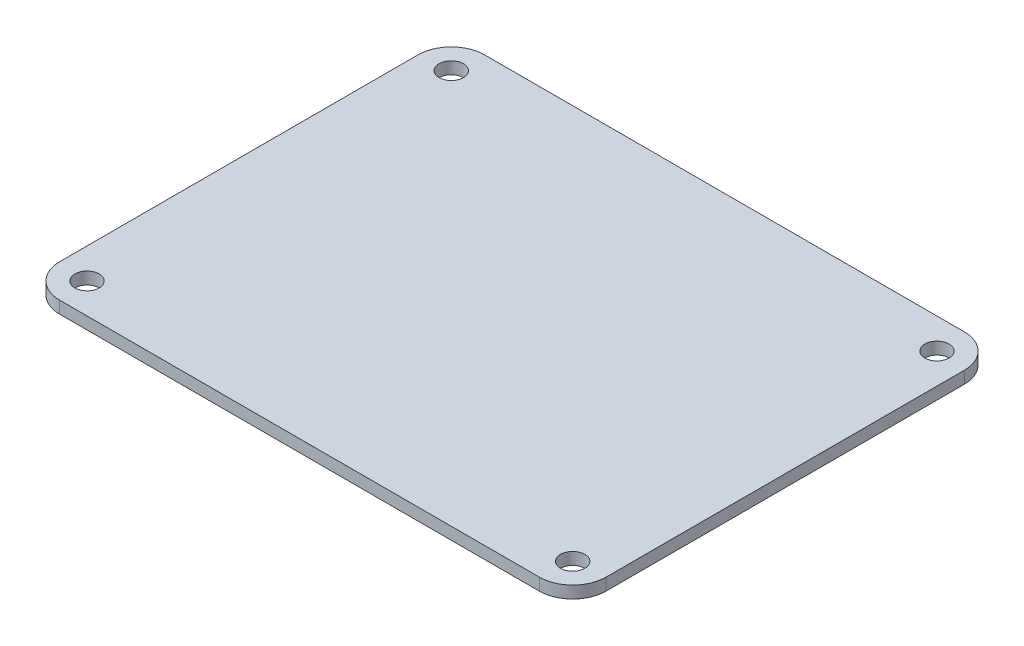
SolidWorks part; units mm, degrees
ref_plane "Front Plane" through (0, 0, 0) normal (0, 0, 1) x (1, 0, 0)
ref_plane "Top Plane" through (0, 0, 0) normal (0, 1, 0) x (1, 0, 0)
ref_plane "Right Plane" through (0, 0, 0) normal (1, 0, 0) x (0, 0, -1)
sketch "Sketch1" plane through (0, 0, 0) normal (0, 1, 0) x (1, 0, 0)
  line L1 (-114.3, 88.9) -> (114.3, 88.9)
  line L2 (-114.3, 88.9) -> (-114.3, -88.9)
  line L3 (-114.3, -88.9) -> (114.3, -88.9)
  line L4 (114.3, 88.9) -> (114.3, -88.9)
  line L5 (-114.3, 88.9) -> (114.3, -88.9) construction
  line L6 (-114.3, -88.9) -> (114.3, 88.9) construction
  point P0 (0, 0)
  dimension "D1" = 177.8
  dimension "10" = 228.6
extrude "Boss-Extrude1" add sketch "Sketch1" along normal blind 5.08
sketch "Sketch2" plane through (0, 5.08, 0) normal (0, 1, 0) x (1, 0, 0)
  line L0 (-101.6, 76.2) -> (-101.6, 88.9) construction
  line L1 (114.3, 88.9) -> (-114.3, 88.9) construction
  line L2 (-101.6, 76.2) -> (-114.3, 76.2) construction
  line L3 (-114.3, 88.9) -> (-114.3, -88.9) construction
  line L4 (-101.6, -76.2) -> (-114.3, -76.2) construction
  line L5 (-101.6, -76.2) -> (-101.6, -88.9) construction
  line L6 (-114.3, -88.9) -> (114.3, -88.9) construction
  line L7 (101.6, 76.2) -> (101.6, 88.9) construction
  line L8 (101.6, 76.2) -> (114.3, 76.2) construction
  line L9 (114.3, -88.9) -> (114.3, 88.9) construction
  line L10 (101.6, -76.2) -> (101.6, -88.9) construction
  line L11 (101.6, -76.2) -> (114.3, -76.2) construction
  circle A0 centre (-101.6, 76.2) radius 5.08
  circle A1 centre (101.6, 76.2) radius 5.08
  circle A2 centre (101.6, -76.2) radius 5.08
  circle A3 centre (-101.6, -76.2) radius 5.08
  dimension "D1" = 10.16
  dimension "D2" = 12.7
extrude "Cut-Extrude1" cut sketch "Sketch2" against normal through all
fillet "Fillet3" radius 13.97 4 edges at (114.3, 2.54, -88.9) (114.3, 2.54, 88.9) (-114.3, 2.54, -88.9) (-114.3, 2.54, 88.9)
